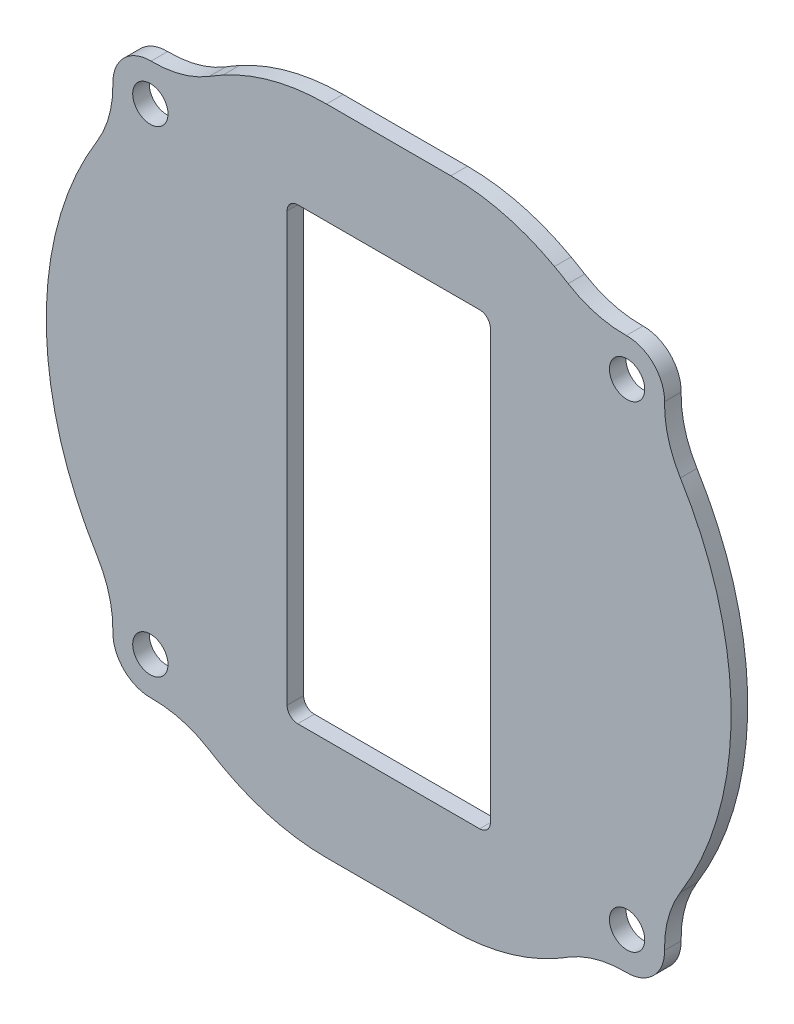
SolidWorks part; units mm, degrees
material "Epoxy, renforcé"
ref_plane "Plan de face" through (0, 0, 0) normal (0, 0, 1) x (1, 0, 0)
ref_plane "Plan de dessus" through (0, 0, 0) normal (0, 1, 0) x (1, 0, 0)
ref_plane "Plan de droite" through (0, 0, 0) normal (1, 0, 0) x (0, 0, -1)
sketch "Esquisse1" plane through (0, 0, 0) normal (0, 0, 1) x (1, 0, 0)
  line L0 (0, 31.5) -> (0, 0) construction
  line L1 (15.5, 21) -> (-15.5, 21) construction
  line L2 (15.5, 21) -> (15.5, -21) construction
  line L3 (15.5, -21) -> (-15.5, -21) construction
  line L4 (-15.5, 21) -> (-15.5, -21) construction
  line L5 (15.5, 21) -> (-15.5, -21) construction
  line L6 (15.5, -21) -> (-15.5, 21) construction
  line L7 (0, 0) -> (-22.2739, 22.2739) construction
  arc A0 (-24.9579, 20.0276) -> (-24.9579, -20.0276) centre (0, 0) ccw
  circle A1 centre (0, 0) radius 31.5 construction
  circle A2 centre (-22.2739, 22.2739) radius 1.65
  circle A3 centre (22.2739, 22.2739) radius 1.65
  circle A4 centre (22.2739, -22.2739) radius 1.65
  circle A5 centre (-22.2739, -22.2739) radius 1.65
  arc A6 (-20.0276, 24.9579) -> (-24.9579, 20.0276) centre (-22.2739, 22.2739) ccw
  arc A7 (24.9579, 20.0276) -> (20.0276, 24.9579) centre (22.2739, 22.2739) ccw
  arc A8 (20.0276, -24.9579) -> (24.9579, -20.0276) centre (22.2739, -22.2739) ccw
  arc A9 (-24.9579, -20.0276) -> (-20.0276, -24.9579) centre (-22.2739, -22.2739) ccw
  arc A10 (20.0276, 24.9579) -> (-20.0276, 24.9579) centre (0, 0) ccw
  arc A11 (24.9579, -20.0276) -> (24.9579, 20.0276) centre (0, 0) ccw
  arc A13 (-20.0276, -24.9579) -> (20.0276, -24.9579) centre (0, 0) ccw
  point P0 (0, 0)
  point P21 (0, 0)
  point P29 (0, 0)
  dimension "D3" = 63
  dimension "D5" = 3.3
  dimension "D7" = 64
  dimension "D9" = 7
  dimension "D1" = 31
  dimension "D2" = 42
  dimension "D4" = 45
  dimension "D6" = 4
  dimension "D8" = 4
extrude "Boss.-Extru.1" add sketch "Esquisse1" along normal blind 1.55
sketch "Esquisse2" plane through (0, 0, 1.55) normal (0, 0, 1) x (1, 0, 0)
  line L1 (9.5, 21) -> (-9.5, 21)
  line L2 (9.5, 21) -> (9.5, -21)
  line L3 (9.5, -21) -> (-9.5, -21)
  line L4 (-9.5, 21) -> (-9.5, -21)
  line L5 (9.5, 21) -> (-9.5, -21) construction
  line L6 (9.5, -21) -> (-9.5, 21) construction
  point P0 (0, 0)
  dimension "D1" = 19
  dimension "D2" = 42
extrude "Enlèv. mat.-Extru.1" cut sketch "Esquisse2" against normal through all
fillet "Congé1" radius 10 8 edges at (24.9579, -20.0276, 0.775) (20.0276, -24.9579, 0.775) (-20.0276, -24.9579, 0.775) (-24.9579, -20.0276, 0.775) (-24.9579, 20.0276, 0.775) (-20.0276, 24.9579, 0.775) (20.0276, 24.9579, 0.775) (24.9579, 20.0276, 0.775)
fillet "Congé2" radius 1 4 edges at (9.5, 21, 0.775) (9.5, -21, 0.775) (-9.5, -21, 0.775) (-9.5, 21, 0.775)
sketch "Esquisse3" plane through (0, 0, 1.55) normal (0, 0, 1) x (1, 0, 0)
  line L1 (35, -30.5) -> (-35, -30.5)
  line L2 (35, -30.5) -> (35, 30.5)
  line L3 (35, 30.5) -> (-35, 30.5)
  line L4 (-35, -30.5) -> (-35, 30.5)
  line L5 (35, -30.5) -> (-35, 30.5) construction
  line L6 (35, 30.5) -> (-35, -30.5) construction
  point P0 (0, 0)
  dimension "D1" = 61
  dimension "D2" = 70
extrude "Enlèv. mat.-Extru.2" cut sketch "Esquisse3" against normal through all flip side to cut
fillet "Congé3" radius 20 4 edges at (9.6825, -30.5, 0.775) (-9.6825, -30.5, 0.775) (9.6825, 30.5, 0.775) (-9.6825, 30.5, 0.775)
